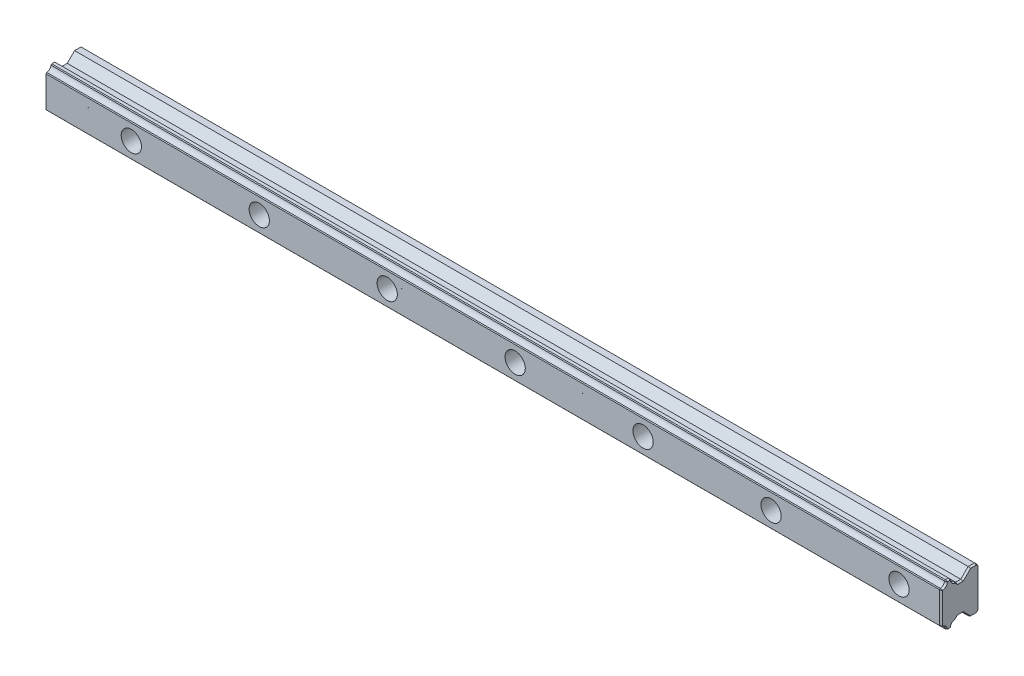
SolidWorks part; units mm, degrees
ref_plane "Front Plane" through (0, 0, 0) normal (0, 0, 1) x (1, 0, 0)
ref_plane "Top Plane" through (0, 0, 0) normal (0, 1, 0) x (1, 0, 0)
ref_plane "Right Plane" through (0, 0, 0) normal (1, 0, 0) x (0, 0, -1)
ref_plane "Plane1" through (980, 0, 0) normal (1, 0, 0) x (0, 0, -1)
sketch "Sketch1" plane through (980, 0, 0) normal (1, 0, 0) x (0, 0, -1)
  line L0 (-9.8799, -6.5501) -> (0, -6.5501)
  line L1 (0, -6.5501) -> (0, 6.5499)
  line L2 (0, 6.5499) -> (-9.8793, 6.5499)
  line L3 (-9.8793, 6.5499) -> (-10.9875, 7.6581)
  line L4 (-12.9186, 9.9999) -> (-17.4, 9.9999)
  line L5 (-17.4, 9.9999) -> (-17.4, -10.0001)
  line L6 (-17.4, -10.0001) -> (-12.9186, -10.0001)
  line L7 (-10.9885, -7.6587) -> (-9.8799, -6.5501)
  arc A0 (-10.9875, 7.6581) -> (-12.9186, 9.9999) centre (-10.8, 9.7798) cw
  arc A1 (-12.9186, -10.0001) -> (-10.9885, -7.6587) centre (-10.8, -9.7803) cw
extrude "Boss-Extrude1" add sketch "Sketch1" against normal blind 1000
sketch "Sketch2" plane through (0, -6.5501, 0) normal (0, -1, 0) x (1, 0, 0)
  line L0 (-20, 7.4501) -> (980, 7.4501)
  line L1 (980, 7.4501) -> (980, 0)
  line L2 (980, 0) -> (-20, 0)
  line L3 (-20, 0) -> (-20, 7.4501)
extrude "Boss-Extrude2" add sketch "Sketch2" along normal blind 3.4499
sketch "Sketch3" plane through (0, 6.5499, 0) normal (0, 1, 0) x (-1, 0, 0)
  line L0 (-980, 0) -> (-980, 3.9998)
  line L1 (-980, 3.9998) -> (20, 3.9998)
  line L2 (20, 3.9998) -> (20, 0)
  line L3 (20, 0) -> (-980, 0)
extrude "Boss-Extrude3" add sketch "Sketch3" along normal blind 3.4501
draft "Draft1" type of draft neutral plane draft angle 45.002 faces to draft 1 face at (480, 8.2749, 3.9998) neutral plane through (0, 10, 0) neutral plane normal (0, 1, 0) parameters "D1"=45.002
draft "Draft2" type of draft neutral plane draft angle 45.004 faces to draft 1 face at (480, -8.2751, 7.4501) neutral plane through (-20, -6.5501, 9.8799) neutral plane normal (0, -1, 0) parameters "D1"=45.004
hole_wizard "Hole1" positions "Sketch5" profile "Sketch4" legacy
sketch "Sketch5" plane through (-20, 0, 0) normal (-1, 0, 0) x (0, 0, 1)
  point P0 (17.1997, 9.7801)
  point P1 (17.1997, -9.7803)
sketch "Sketch4" plane through (-20, 9.7801, 17.1997) normal (0, 1, 0) x (0, 0, 1)
  line L0 (0, 0) -> (0, 1000)
  line L1 (0, 1000) -> (2.13, 1000)
  line L2 (2.13, 1000) -> (2.13, 0)
  line L3 (2.13, 0) -> (0, 0)
  line L4 (0, 110) -> (0, -10) construction
  dimension "Diameter" = 4.26
  dimension "Depth" = 1000
hole_wizard "Hole2" positions "Sketch7" profile "Sketch6" legacy
sketch "Sketch7" plane through (0, 0, 17.4) normal (0, 0, 1) x (1, 0, 0)
  point P0 (960, 0)
  point P1 (900, 0)
  point P2 (840, 0)
  point P3 (780, 0)
  point P4 (720, 0)
  point P5 (660, 0)
  point P6 (600, 0)
  point P7 (540, 0)
  point P8 (480, 0)
  point P9 (420, 0)
  point P10 (360, 0)
  point P11 (300, 0)
  point P12 (240, 0)
  point P13 (180, 0)
  point P14 (120, 0)
  point P15 (60, 0)
  point P16 (0, 0)
sketch "Sketch6" plane through (960, 0, 17.4) normal (1, 0, 0) x (0, -1, 0)
  line L0 (0, 0) -> (0, 17.4)
  line L1 (0, 17.4) -> (3, 17.4)
  line L2 (3, 17.4) -> (3, 8.4)
  line L3 (3, 8.4) -> (4.75, 8.4)
  line L4 (4.75, 8.4) -> (4.75, 0)
  line L5 (4.75, 0) -> (0, 0)
  line L6 (0, 110) -> (0, -10) construction
  dimension "Diameter" = 6
  dimension "Depth" = 17.4
  dimension "C-Bore Diameter" = 9.5
  dimension "C-Bore Depth" = 8.4
chamfer "Chamfer1" distance 0.372 angle 45 1 edges at (480, -10.0001, 12.9186)
chamfer "Chamfer2" distance 0.362 angle 45 4 edges at (480, 9.9999, 15.0811) (480, -10.0001, 15.0811) (480, 7.6595, 17.4) (480, -7.6597, 17.4)
chamfer "Chamfer3" distance 1 angle 45 2 edges at (480, -10, 0) (480, 10, 0)
chamfer "Chamfer4" distance 0.3715 angle 45 1 edges at (480, 9.9999, 12.9186)
chamfer "Chamfer5" distance 0.364 angle 70 48 edges at (980, -10.0001, 14.0049) (-20, -10.0001, 14.0049) (-20, -8.2824, 15.6854) (980, -8.2824, 15.6854) (980, -8.2894, 12.3212) (-20, -8.2894, 12.3212) (980, -0.0001, 17.4) (-20, -0.0001, 17.4) (980, -7.1044, 10.4342) (-20, -7.1044, 10.4342) (-20, -6.5501, 8.665) (980, -6.5501, 8.665) (-20, -8.2751, 5.7249) (980, 8.2821, 15.6854) (-20, 8.2821, 15.6854) (-20, -10, 2.4999) (980, 9.9999, 14.0046) (-20, 9.9999, 14.0046) (-20, -9.5, 0.5) (980, -9.5, 0.5) (980, 0, 0) (-20, 0, 0) (-20, 8.2888, 12.3211) (980, 8.2888, 12.3211) (980, 9.5, 0.5) (-20, 9.5, 0.5) (980, 7.104, 10.4334) (-20, 7.104, 10.4334) (-20, 10, 2.4999) (980, 6.5499, 8.6647) (-20, 6.5499, 8.6647) (-20, 8.2749, 5.725) (980, 8.2749, 5.725) (980, 10, 2.4999) (-20, 9.8173, 13.1076) (980, 9.8173, 13.1076) (980, 9.8224, 14.8966) (-20, 9.8224, 14.8966) (980, -10, 2.4999) (980, -8.2751, 5.7249) (-20, 7.4767, 17.2208) (980, 7.4767, 17.2208) (980, -7.477, 17.2208) (-20, -7.477, 17.2208) (-20, -9.8173, 13.1078) (980, -9.8173, 13.1078) (-20, -9.8227, 14.8966) (980, -9.8227, 14.8966)
sketch "Sketch8" plane through (0, 0, 17.4) normal (0, 0, 1) x (1, 0, 0)
  line L0 (-20, 11.7567) -> (560, 11.7567)
  line L1 (-20, 11.7567) -> (-20, -10.0001)
  line L2 (-20, -10.0001) -> (560, -10.0001)
  line L3 (560, 11.7567) -> (560, -10.0001)
  line L5 (980, 7.1468) -> (980, -7.147) construction
  line L7 (-20, -6.7542) -> (-20, 6.7539) construction
  line L8 (979, -10.0001) -> (-19.636, -10.0001) construction
  point P4 (236.6404, -9.6453)
  point P5 (0, 0)
  point P9 (178.0627, 28.5087)
  point P10 (0, 0)
  point P15 (-20, 9.9999)
  dimension "D1" = 420
extrude "Cut-Extrude1" cut sketch "Sketch8" against normal through all
